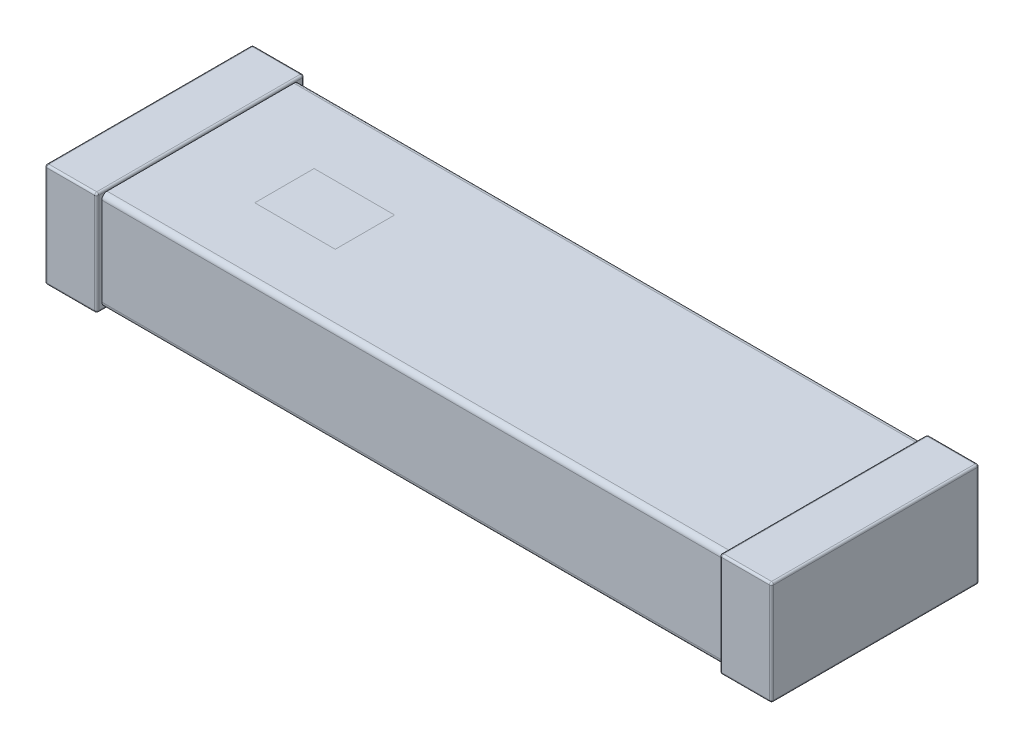
SolidWorks part; units mm, degrees
ref_plane "Ebene vorne" through (0, 0, 0) normal (0, 0, 1) x (1, 0, 0)
ref_plane "Ebene oben" through (0, 0, 0) normal (0, 1, 0) x (1, 0, 0)
ref_plane "Ebene rechts" through (0, 0, 0) normal (1, 0, 0) x (0, 0, -1)
sketch "Skizze1" plane through (0, 0, 0) normal (0, 1, 0) x (1, 0, 0)
  line L0 (0, 1.6154) -> (0, 2.6042)
  line L1 (-3, 0.95) -> (3, 0.95)
  line L2 (-3, 0.95) -> (-3, -0.95)
  line L3 (-3, -0.95) -> (3, -0.95)
  line L4 (3, 0.95) -> (3, -0.95)
  line L5 (-3, 0.95) -> (3, -0.95) construction
  line L6 (-3, -0.95) -> (3, 0.95) construction
  line L11 (-3.5, 1) -> (-3, 1)
  line L12 (-3.5, 1) -> (-3.5, -1)
  line L13 (-3.5, -1) -> (-3, -1)
  line L14 (-3, 1) -> (-3, -1)
  line L15 (-3.5, 1) -> (-3, -1) construction
  line L16 (-3.5, -1) -> (-3, 1) construction
  line L17 (3.5, 1) -> (3, -1) construction
  line L18 (3.5, -1) -> (3, -1)
  line L19 (3.5, -1) -> (3, 1) construction
  line L20 (3, 1) -> (3, -1)
  line L21 (3.5, 1) -> (3, 1)
  line L22 (3.5, 1) -> (3.5, -1)
  point P0 (0, 0)
  point P6 (-3.25, 0)
  point P17 (3.25, 0)
  dimension "D1" = 0
  dimension "D2" = 3.25
extrude "Aufsatz-Linear austragen1" add sketch "Skizze1" along normal blind 1 contours L14 L11 L12 L13 L2 | L22 L21 L20 L4 L18 region at (-3.25, 0, 0) region at (3.25, 0, 0)
extrude "Aufsatz-Linear austragen2" add sketch "Skizze1<3>" along normal blind 0.95 from offset 0.025 separate body contours L4 L1 L2 L3 region at (0, 0, 0)
sketch "Skizze1<3>" plane through (0, 0, 0) normal (0, 1, 0) x (1, 0, 0) same geometry as "Skizze1"
fillet "Verrundung1" radius 0.02 12 edges at (-3, 0.5, 1) (-3, 1, 0) (-3, 0.5, -1) (-3, 0, 0) (-3.5, 0.5, -1) (-3.5, 1, 0) (-3.5, 0.5, 1) (-3.5, 0, 0) (-3.25, 0, -1) (-3.25, 1, -1) (-3.25, 1, 1) (-3.25, 0, 1)
fillet "Verrundung3" radius 0.02 12 edges at (3.25, 0, -1) (3, 0.5, -1) (3, 0, 0) (3, 0.5, 1) (3.25, 0, 1) (3.25, 1, 1) (3, 1, 0) (3.25, 1, -1) (3.5, 0.5, 1) (3.5, 1, 0) (3.5, 0.5, -1) (3.5, 0, 0)
sketch "Skizze2" plane through (0, 0.975, 0) normal (0, 1, 0) x (1, 0, 0)
  line L1 (-2.1918, 0.2858) -> (-1.4164, 0.2858)
  line L2 (-2.1918, 0.2858) -> (-2.1918, -0.2858)
  line L3 (-2.1918, -0.2858) -> (-1.4164, -0.2858)
  line L4 (-1.4164, 0.2858) -> (-1.4164, -0.2858)
  line L5 (-2.1918, 0.2858) -> (-1.4164, -0.2858) construction
  line L6 (-2.1918, -0.2858) -> (-1.4164, 0.2858) construction
  point P0 (-1.8041, 0)
split line "Trennlinie1"
fillet "Verrundung4" radius 0.05 4 edges at (0, 0.025, -0.95) (0, 0.975, -0.95) (0, 0.025, 0.95) (0, 0.975, 0.95)
